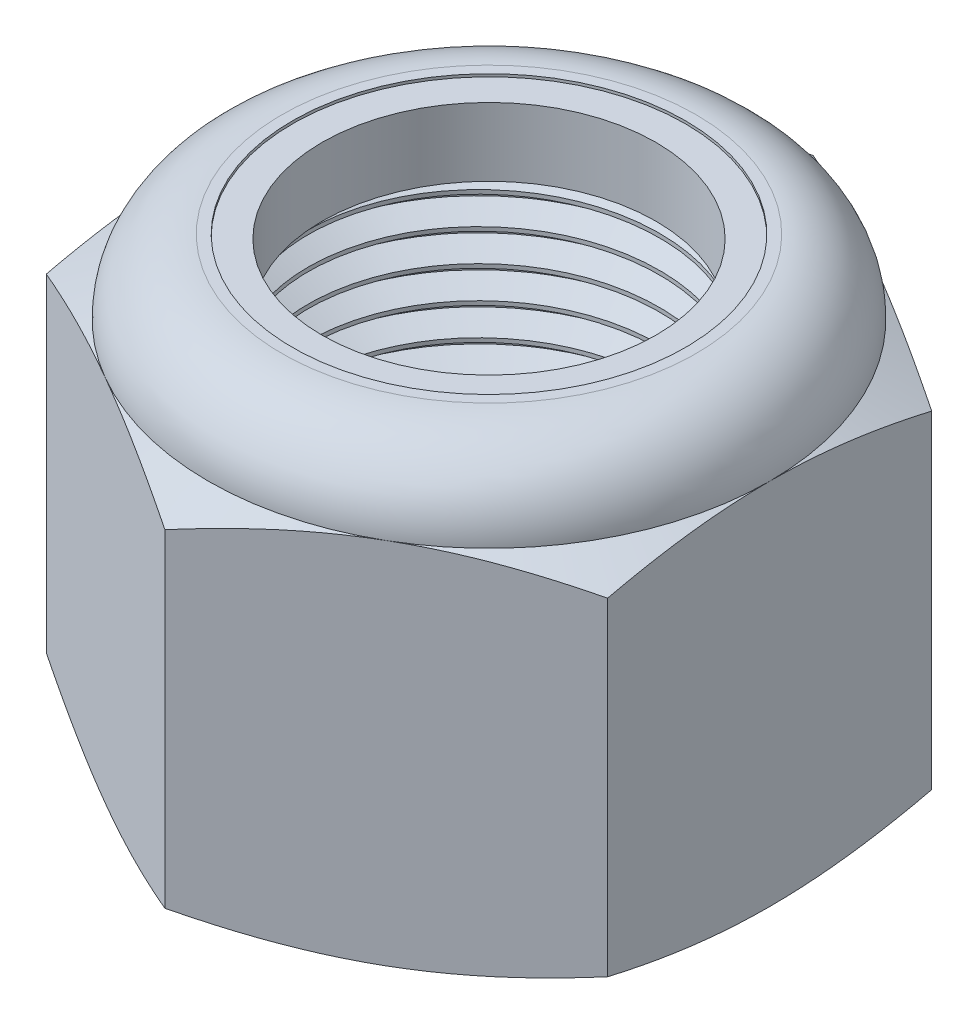
SolidWorks part; units mm, degrees
note: '?' marks a value the reader was unsure of.
ref_plane "Front" through (0, 0, 0) normal (0, 0, 1) x (1, 0, 0)
ref_plane "Top" through (0, 0, 0) normal (0, 1, 0) x (1, 0, 0)
ref_plane "Right" through (0, 0, 0) normal (1, 0, 0) x (0, 0, -1)
sketch "Sketch8" plane through (0, 0, 0) normal (1, 0, 0) x (0, 0, -1)
  line L0 (0, 0) -> (0, 25.0031) construction
  line L1 (15.875, 0) -> (-15.875, 0) construction
  line L2 (-11.1125, 25.0031) -> (11.1125, 25.0031) construction
  line L3 (11.1125, 25.0031) -> (11.1125, 23.1888) construction
sketch "Sketch1" plane through (0, 0, 0) normal (0, 1, 0) x (1, 0, 0)
  line L1 (0, 18.3309) -> (-15.875, 9.1654)
  line L2 (-15.875, 9.1654) -> (-15.875, -9.1654)
  line L3 (-15.875, -9.1654) -> (0, -18.3309)
  line L4 (0, -18.3309) -> (15.875, -9.1654)
  line L5 (15.875, -9.1654) -> (15.875, 9.1654)
  line L6 (15.875, 9.1654) -> (0, 18.3309)
  circle A0 centre (0, 0) radius 15.875 construction
  circle A1 centre (0, 0) radius 11.1125
extrude "Extrude1" add sketch "Sketch1" along normal up to vertex (25.0031 mm away) up to point (0, 25.0031, 0)
sketch "Sketch5" plane through (0, 0, 0) normal (1, 0, 0) x (0, 0, -1)
  line L0 (0, 0) -> (15.875, 0)
  line L1 (15.875, 0) -> (18.3309, 1.1452)
  line L2 (18.3309, 1.1452) -> (18.3309, 19.6907)
  line L3 (18.3309, 19.6907) -> (15.875, 20.8359)
  line L4 (11.7078, 25.0031) -> (11.7078, 26.2731)
  line L5 (11.7078, 26.2731) -> (19.6009, 26.2731)
  line L6 (19.6009, 26.2731) -> (19.6009, -1.27)
  line L7 (19.6009, -1.27) -> (0, -1.27)
  line L8 (0, -1.27) -> (0, 0)
  line L9 (15.875, 20.8359) -> (15.875, 0) construction
  line L12 (18.3309, 25.0031) -> (18.3309, 0) construction
  line L13 (18.3309, 12.5016) -> (19.6009, 12.5016) construction
  line L15 (0, 0) -> (0, 26.2731) construction
  line L18 (15.875, 0) -> (-15.875, 0) construction
  line L19 (9.1654, 25.0031) -> (18.3309, 25.0031) construction
  line L20 (0, 26.2731) -> (11.7078, 26.2731) construction
  line L21 (9.1654, 0) -> (18.3309, 0) construction
  arc A0 (15.875, 20.8359) -> (11.7078, 25.0031) centre (11.7078, 20.8359) ccw
  dimension "D1" = 25
  dimension "D2" = 1.27
  dimension "D4" = 4.1672
revolve "Cut-Revolve3" cut sketch "Sketch5" angle 360 about L15
sketch "Sketch4" plane through (0, 0, 0) normal (1, 0, 0) x (0, 0, -1)
  line L0 (0, 20.8359) -> (12.2237, 20.8359)
  line L1 (12.2237, 20.8359) -> (0, 15.1359)
  line L3 (0, 5.7) -> (12.2237, 0)
  line L4 (12.2237, 0) -> (0, 0)
  line L5 (0, 0) -> (0, 20.8359) construction
  line L10 (0, 0) -> (0, 25.0031) construction
  line L11 (0, 5.7) -> (0, 0)
  line L12 (0, 20.8359) -> (0, 15.1359)
  line L13 (13.7482, 20.8359) -> (0, 20.8359) construction
  dimension "D1" = 25
  dimension "D2" = 24.4475
sketch "Sketch6" plane through (0, 0, 0) normal (1, 0, 0) x (0, 0, -1)
  line L0 (0, 20.8359) -> (15.7226, 20.8359)
  line L1 (11.7078, 24.8507) -> (5.8539, 24.8507)
  line L2 (0, 26.2731) -> (0, 20.8359)
  line L3 (5.8539, 26.2731) -> (0, 26.2731)
  line L4 (0, 26.2731) -> (11.7078, 26.2731) construction
  line L5 (0, 0) -> (0, 26.2731) construction
  line L6 (0, 26.2731) -> (0, 0) construction
  line L7 (5.8539, 24.8507) -> (5.8539, 26.2731)
  line L8 (11.7078, 25.0031) -> (11.7078, 24.8507) construction
  line L9 (5.8539, 24.8507) -> (0, 24.8507) construction
  line L10 (0, 24.8507) -> (0, 15.1359) construction
  arc A0 (15.7226, 20.8359) -> (11.7078, 24.8507) centre (11.7078, 20.8359) ccw
  arc A1 (15.875, 20.8359) -> (11.7078, 25.0031) centre (11.7078, 20.8359) ccw construction
  dimension "D1" = 0.1524
revolve "Cut-Revolve4" cut sketch "Sketch6" angle 360 about L6
revolve "Cut-Revolve2" cut sketch "Sketch4" angle 360 about L5
sketch "Sketch7" plane through (0, 0, 0) normal (1, 0, 0) x (0, 0, -1)
  line L0 (9.4456, 20.9121) -> (15.6457, 20.9121)
  line L1 (11.7078, 24.7745) -> (9.4456, 24.7745)
  line L2 (9.4456, 24.7745) -> (9.4456, 20.9121)
  line L3 (9.4456, 20.9121) -> (0, 20.9121) construction
  line L4 (0, 20.9121) -> (0, 24.7745) construction
  line L5 (0, 24.7745) -> (9.4456, 24.7745) construction
  line L6 (9.4456, 20.9121) -> (9.4456, 20.8359) construction
  line L7 (0, 20.8359) -> (15.7226, 20.8359) construction
  line L8 (11.7078, 24.7745) -> (11.7078, 24.8507) construction
  arc A0 (15.6457, 20.9121) -> (11.7078, 24.7745) centre (11.7078, 20.8359) ccw
  arc A2 (15.7226, 20.8359) -> (11.7078, 24.8507) centre (11.7078, 20.8359) ccw construction
  dimension "D1" = 0.0762
  dimension "D2" = 18.8912
revolve "Revolve2" add sketch "Sketch7" angle 360 about L4
sketch "Sketch2" plane through (0, 0, 0) normal (1, 0, 0) x (0, 0, -1)
  line L0 (-11.1125, 0) -> (-11.1125, 20.8359) construction
  line L1 (0, 0) -> (11.1125, 0)
  line L2 (0, 0) -> (0, 20.8359)
  line L3 (0, 20.8359) -> (11.1125, 20.8359)
  line L4 (11.1125, 0) -> (11.1125, 20.8359)
  line L6 (13.7482, 20.8359) -> (15.875, 20.8359) construction
  line L7 (0, -11.1125) -> (0, 0) construction
revolve "Revolve1" add sketch "Sketch2" angle 360 about L7
sketch "Sketch9" plane through (0, 0, 0) normal (1, 0, 0) x (0, 0, -1)
  line L0 (11.3089, 22.5368) -> (11.3089, 20.7225) construction
  line L1 (11.3089, 20.7225) -> (9.7377, 21.6297) construction
  line L2 (9.7377, 21.6297) -> (11.3089, 22.5368) construction
  line L3 (9.9341, 21.7431) -> (9.9341, 21.5163) construction
  line L4 (11.1125, 22.4234) -> (11.1125, 20.8359) construction
  line L5 (9.7377, 21.6297) -> (9.9341, 21.6297) construction
  line L6 (11.1125, 21.6297) -> (11.3089, 21.6297) construction
  line L7 (11.2107, 21.6297) -> (11.2107, 22.4801) construction
  line L8 (11.3089, 20.7225) -> (11.2107, 22.4801)
  line L9 (11.2107, 22.4801) -> (9.9341, 21.7431)
  line L10 (9.9341, 21.7431) -> (9.9341, 21.5163)
  line L11 (9.9341, 21.5163) -> (11.3089, 20.7225)
  dimension "D1" = 1.8143
  dimension "D2" = 0.2268
sketch "Sketch10" plane through (0, 20.8359, 0) normal (0, 1, 0) x (1, 0, 0)
  circle A1 centre (0, 0) radius 11.1125
  circle A2 centre (0, 0) radius 11.1125
  dimension "D1" = 0
curve "Helix/Spiral1" pitch 1.8143 height 26.8174 turns 14.7813
sweep "Cut-Sweep1" cut profiles "Sketch9" path "Helix/Spiral1" align with end faces yes
sketch "Sketch11" plane through (0, 0, 0) normal (1, 0, 0) x (0, 0, -1)
  line L0 (0, 0) -> (0, 25.0031) construction
  line L1 (15.875, 0) -> (-15.875, 0) construction
  line L4 (0, 25.0031) -> (0, 0) construction
  line L5 (0, 12.5016) -> (11.1125, 12.5016) construction
  line L6 (0, 0) -> (12.2238, 0)
  line L7 (0, 5.7) -> (0, 0)
  line L8 (12.2238, 0) -> (0, 5.7)
  dimension "D1" = 24.4475
  dimension "D2" = 25
revolve "Revolve3" add sketch "Sketch11" angle 360 about L4
sketch "Sketch12" plane through (0, 0, 0) normal (1, 0, 0) x (0, 0, -1)
  line L0 (12.2237, 20.8359) -> (0, 20.8359)
  line L1 (0, 20.8359) -> (0, 0)
  line L2 (0, 0) -> (12.2237, 0)
  line L3 (15.875, 0) -> (-15.875, 0) construction
  line L4 (12.2237, 0) -> (12.2237, 20.8359)
  line L5 (-12.2237, 0) -> (12.2237, 0) construction
revolve "Revolve4" add sketch "Sketch12" angle 360 about L0
combine bodies "Combine1" operation type subtract main body 136 bodies to subtract 133
ref_plane "Contact Plane 1" through (0, 0, 0) normal (0, -1, 0) x (1, 0, 0)
ref_axis "Center Axis 1" through (0, -2.1015, 0) along (0, 1, 0)?
equation "\"D4@Sketch5\"=\"Height@Sketch8\"/6"
equation "\"D1@Sketch9\"=\"Thread Pitch@Sketch8\""
equation "\"D2@Sketch9\"=\"Thread Pitch@Sketch8\"/8"
equation "\"D4@Helix/Spiral1\"=\"Thread Pitch@Sketch8\""
equation "\"D3@Helix/Spiral1\"=\"Thread Pitch@Sketch8\"+\"Height@Sketch8\""
equation "\"D2@Sketch4\"=\"Thread Dia@Sketch8\"*1.1"
equation "\"D1@Sketch11\"=\"Thread Dia@Sketch8\"*1.1"
equation "\"D2@Sketch7\"=\"Thread Dia@Sketch8\"*.85"
